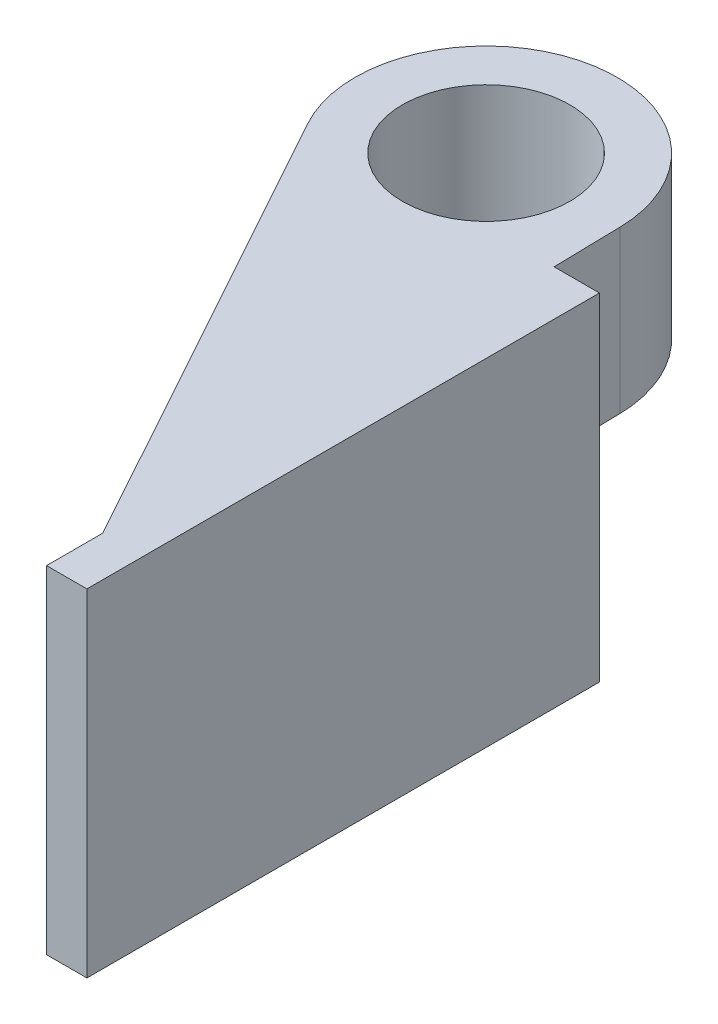
SolidWorks part; units mm, degrees
note: The reader was unsure of these and kept them because the rebuilt part matched: shared geometry of "Sketch1<3>".
ref_plane "Front Plane" through (0, 0, 0) normal (0, 0, 1) x (1, 0, 0)
ref_plane "Top Plane" through (0, 0, 0) normal (0, 1, 0) x (1, 0, 0)
ref_plane "Right Plane" through (0, 0, 0) normal (1, 0, 0) x (0, 0, -1)
sketch "Sketch1" plane through (0, 0, 0) normal (0, 1, 0) x (1, 0, 0)
  line L0 (-5.6917, -3.1391) -> (2.049, -17.1741)
  line L1 (6.8126, -15.8977) -> (6.4988, 0.1273)
  line L2 (10, -10) -> (12.1837, -10) construction
  line L7 (-10, -10) -> (10, -10) construction
  line L8 (-10, -10) -> (-10, 30.7) construction
  line L9 (-10, 30.7) -> (10, 30.7) construction
  line L10 (10, -10) -> (10, 30.7) construction
  line L11 (6.8131, -3.1977) -> (6.5639, -3.1977)
  line L12 (6.8131, -3.1977) -> (8.8131, -3.1977)
  line L13 (6.8131, -3.1977) -> (6.8131, -28.5977)
  line L14 (6.8131, -28.5977) -> (8.8131, -28.5977)
  line L15 (8.8131, -3.1977) -> (8.8131, -28.5977)
  line L16 (4.2731, -15.9474) -> (0, 0) construction
  line L17 (8.8131, -3.1977) -> (11.9881, -3.1977) construction
  line L18 (8.8131, -3.1977) -> (8.8131, -28.5977) construction
  line L19 (8.8131, -28.5977) -> (11.9881, -28.5977) construction
  line L20 (11.9881, -3.1977) -> (11.9881, -28.5977) construction
  line L21 (4.2731, -15.9474) -> (0, -15.9474) construction
  line L22 (2.049, -17.1741) -> (6.8131, -25.8122)
  circle A0 centre (0, 0) radius 6.5
  arc A1 (2.049, -17.1741) -> (6.8126, -15.8977) centre (4.2731, -15.9474) ccw
  circle A2 centre (0, 0) radius 16.51 construction
  circle A3 centre (0, 0) radius 7.5262 construction
  circle A4 centre (101.0151, -15.8977) radius 89.027 construction
  point P6 (8.8131, -15.8977)
  point P8 (4.9305, -18.4009)
  point P12 (0, -10)
  dimension "D1" = 13
  dimension "D5" = 2
  dimension "D9" = 2.54
  dimension "D11" = 178.054
  dimension "D2" = 75
  dimension "D3" = 19.05
  dimension "D4" = 25.4
  dimension "D6" = 10
  dimension "D7" = 40.7
  dimension "D8" = 20
  dimension "D10" = 3.175
extrude "Boss-Extrude1" add sketch "Sketch1" along normal mid plane 8
extrude "Boss-Extrude2" add sketch "Sketch1<3>" against normal blind 12.7 and the other way blind 4
sketch "Sketch1<3>" plane through (0, 0, 0) normal (0, 1, 0) x (1, 0, 0) same geometry as "Sketch1"
sketch "Sketch2" plane through (0, -4, 0) normal (0, -1, 0) x (1, 0, 0)
  circle A0 centre (0, 0) radius 4.15
  dimension "D1" = 8.3
extrude "Cut-Extrude1" cut sketch "Sketch2" along normal blind 5.95 from surface at -8 starting at face at (5.2196, 4, 12.0901)
sketch "Sketch3" plane through (0, -4, 0) normal (0, -1, 0) x (1, 0, 0)
  circle A0 centre (0, 0) radius 1.6
  dimension "mm" = 3.2
extrude "Cut-Extrude2" cut sketch "Sketch3" against normal through all
mirror "Mirror3" [suppressed]
sketch "Sketch5" plane through (0, -12.7, 0) normal (0, -1, 0) x (1, 0, 0)
  line L0 (6.8131, 28.5977) -> (8.8131, 28.5977) construction
  line L1 (7.8131, 28.5977) -> (-6.5, 28.5977)
  line L2 (7.8131, 28.5977) -> (7.8131, -6.5)
  line L3 (7.8131, -6.5) -> (-6.5, -6.5)
  line L4 (-6.5, 28.5977) -> (-6.5, -6.5)
  arc A0 (-5.6917, 3.1391) -> (6.4988, -0.1273) centre (0, 0) ccw construction
extrude "Cut-Extrude3" [suppressed] cut sketch "Sketch5" against normal through all both and the other way through all
